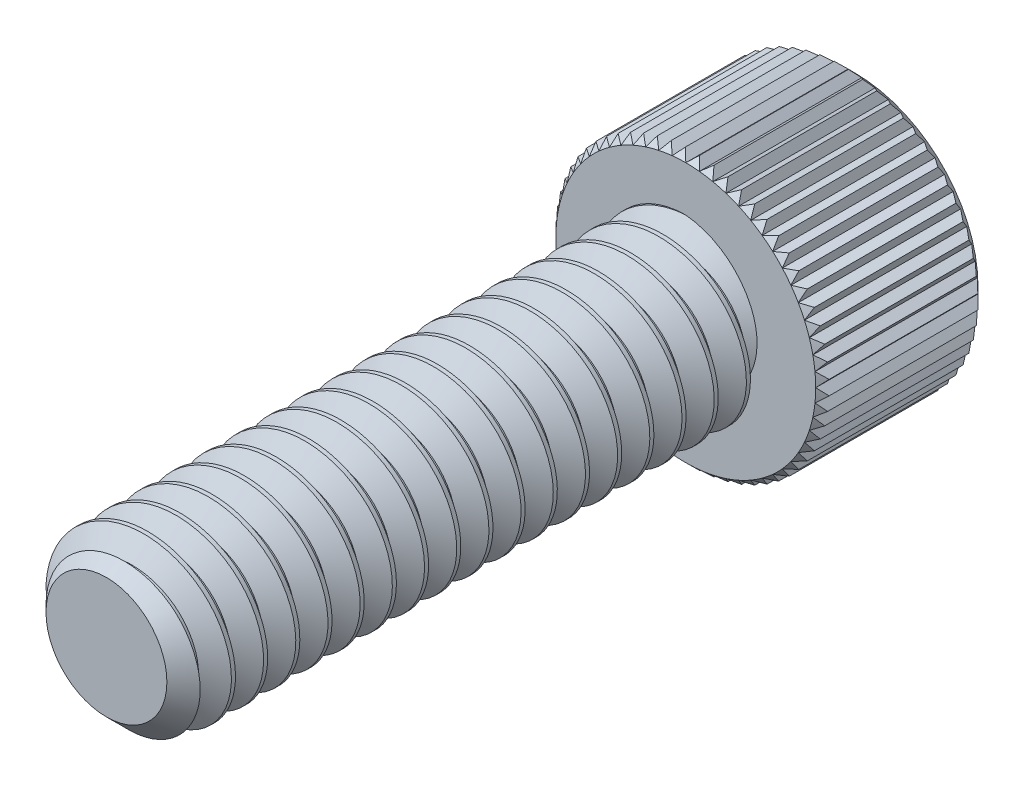
SolidWorks part; units mm, degrees
ref_plane "Front Plane" through (0, 0, 0) normal (0, 0, 1) x (1, 0, 0)
ref_plane "Top Plane" through (0, 0, 0) normal (0, 1, 0) x (1, 0, 0)
ref_plane "Right Plane" through (0, 0, 0) normal (1, 0, 0) x (0, 0, -1)
sketch "Sketch0" plane through (0, 0, 0) normal (1, 0, 0) x (0, 0, -1)
  line L0 (0, 0) -> (6.35, 0) construction
  point P2 (8.2042, 0)
  point P4 (0.254, 0)
  dimension "D1" = 6.35
  dimension "D2" = 1.8542
  dimension "Min Thread" = 0.254
sketch "Sketch1" plane through (0, 0, 0) normal (0, 0, 1) x (1, 0, 0)
  circle A0 centre (0, 0) radius 0.9271
  dimension "OD" = 1.8542
extrude "Extrude1" add sketch "Sketch1" against normal blind 6.35
sketch "Sketch2" plane through (0, 0, 0) normal (0, 0, 1) x (1, 0, 0)
  circle A0 centre (0, 0) radius 0.9271 construction
  circle A1 centre (0, 0) radius 0.9271
curve "Helix/Spiral1" pitch 0.3528 height 6.7028 radius 0.9271 centre (0, 0, 0) axis (0, 0, -1) start towards (0, 1, 0) parameters "pitch"=0.3528
chamfer "Chamfer3" distance 0.2646 angle 45 1 edges at (0.9271, 0, 0)
sketch "Sketch3" plane through (0, 0, 0) normal (1, 0, 0) x (0, 0, -1)
  line L0 (-0.3087, 0.9271) -> (-0.1764, 0.698)
  line L1 (-0.1764, 0.698) -> (-0.1323, 0.698)
  line L2 (-0.1323, 0.698) -> (0, 0.9271)
  line L3 (-0.3087, 0.9271) -> (0, 0.9271)
  line L4 (-0.1543, 0.9271) -> (-0.1543, 0.698) construction
  line L5 (-0.2425, 0.8125) -> (-0.0661, 0.8125) construction
  line L6 (0, 0.9271) -> (0, -0.9271) construction
  dimension "D1" = 0.0441
  dimension "D2" = 0.1764
  dimension "D3" = 60
sweep "Cut-Sweep1" cut profiles "Sketch3" path "Helix/Spiral1" align with end faces yes
sketch "Sketch5" plane through (0, 0, 0) normal (1, 0, 0) x (0, 0, -1)
  line L0 (6.35, -0.7038) -> (6.35, 0.6615) construction
  line L1 (6.35, 0.9271) -> (0.254, 0.9271)
  line L2 (6.35, 0.9271) -> (6.35, 0)
  line L3 (6.35, 0) -> (-0.0834, 0)
  line L4 (0, 0) -> (6.35, 0) construction
  line L5 (0.254, 0.9271) -> (-0.0834, 0)
  line L6 (0, 0) -> (8.89, 0) construction
  dimension "D1" = 70
  dimension "D3" = 2.54
revolve "partially thread" [suppressed] add sketch "Sketch5" angle 360 about L6
sketch "Sketch6" plane through (0, 0, -6.35) normal (0, 0, -1) x (-1, 0, 0)
  circle A0 centre (0, 0) radius 1.4986
  dimension "head dia" = 2.9972
extrude "Extrude2" add sketch "Sketch6" along normal blind 1.8542
sketch "Sketch7" plane through (0, 0, -8.2042) normal (0, 0, -1) x (-1, 0, 0)
  line L1 (0, 0.9165) -> (-0.7937, 0.4583)
  line L2 (-0.7937, 0.4583) -> (-0.7937, -0.4583)
  line L3 (-0.7937, -0.4583) -> (0, -0.9165)
  line L4 (0, -0.9165) -> (0.7938, -0.4583)
  line L5 (0.7938, -0.4583) -> (0.7937, 0.4583)
  line L6 (0.7937, 0.4583) -> (0, 0.9165)
  circle A0 centre (0, 0) radius 0.7937 construction
  dimension "hex dia" = 1.5875
extrude "Cut-Extrude1" cut sketch "Sketch7" against normal blind 1.1906
sketch "Sketch8" plane through (0, 0, -8.2042) normal (0, 0, -1) x (-1, 0, 0)
  circle A0 centre (0, 0) radius 0.9165
extrude "Cut-Extrude2" cut sketch "Sketch8" against normal through all draft 45
chamfer "Chamfer1" distance 0.1499 angle 45 1 edges at (-1.4986, 0, -8.2042)
chamfer "Chamfer2" distance 0.0749 angle 45 1 edges at (-1.4986, 0, -6.35)
sketch "Sketch9" plane through (0, 0, 0) normal (1, 0, 0) x (0, 0, -1)
  line L0 (0, 0.9271) -> (0, -0.9271) construction
  line L1 (0.8819, 0.9271) -> (0.8819, -0.9271) construction
  line L2 (8.2042, 1.4986) -> (8.2042, -1.4986) construction
  line L3 (6.35, 1.4986) -> (6.35, -1.4986) construction
  line L4 (6.35, 1.4237) -> (6.35, -1.4237) construction
  line L5 (8.2042, -1.3487) -> (8.2042, 1.3487) construction
  line L6 (6.35, -1.4986) -> (6.35, 1.4986) construction
  line L7 (0, 0.6625) -> (0, -0.6625) construction
  line L8 (-0.3087, 0.9271) -> (0, 0.9271) construction
  line L9 (0.8819, 0) -> (0, 0) construction
  dimension "D1" = 0.8819
sketch "Sketch10" plane through (0, 0, -6.35) normal (0, 0, 1) x (1, 0, 0)
  line L0 (-0.1613, 1.5735) -> (0, 1.4237)
  line L1 (0, 1.4237) -> (0.1613, 1.5735)
  line L2 (0, 1.4237) -> (0, 1.5735) construction
  line L3 (-0.1613, 1.5735) -> (0.1613, 1.5735)
  line L4 (0, -1.9618) -> (0, 1.9618) construction
  line L5 (0, 0) -> (0.0784, 1.4965) construction
  line L6 (-0.0784, 1.4965) -> (0, 0) construction
  circle A2 centre (0, 0) radius 1.4986 construction
  circle A5 centre (0, 0) radius 1.4237 construction
  dimension "D1" = 6
  dimension "D2" = 0.1499
extrude "Cut-Extrude3" cut sketch "Sketch10" against normal through all
pattern_circular "CirPattern1" count 60 over 360 about axis through (0, 0, -8.2042) along (0, 0, 1) of "Cut-Extrude3"
ref_plane "Contact Plane 1" through (0, 0, -6.35) normal (0, 0, 1) x (1, 0, 0)
ref_axis "Center Axis 1" through (0, 0, 0.8878) along (0, 0, -1)
equation "\"D3@Helix/Spiral1\" = \"screw length@Extrude1\"+\"pitch@Helix/Spiral1\""
equation "\"D1@Sketch3\" = \"pitch@Helix/Spiral1\"*.125"
equation "\"D2@Sketch3\" = \"pitch@Helix/Spiral1\"*.5"
equation "\"D1@Cut-Extrude1\" = \"hex dia@Sketch7\"*.75"
equation "\"D1@Chamfer1\" = \"head dia@Sketch6\"*.05"
equation "\"D1@Sketch9\" = \"pitch@Helix/Spiral1\"*2.50"
equation "\"D1@Chamfer2\" = \"D1@Chamfer1\"/2"
equation "\"D1@Chamfer3\" = \"pitch@Helix/Spiral1\"*.750"
equation "\"D1@Sketch0\" = \"screw length@Extrude1\""
equation "\"D2@Sketch0\" = \"head depth@Extrude2\""
equation "\"D2@Sketch10\"=\"D1@Chamfer1\""
equation "\"D1@CirPattern1\"=\"D3@CirPattern1\"/\"D1@Sketch10\""
